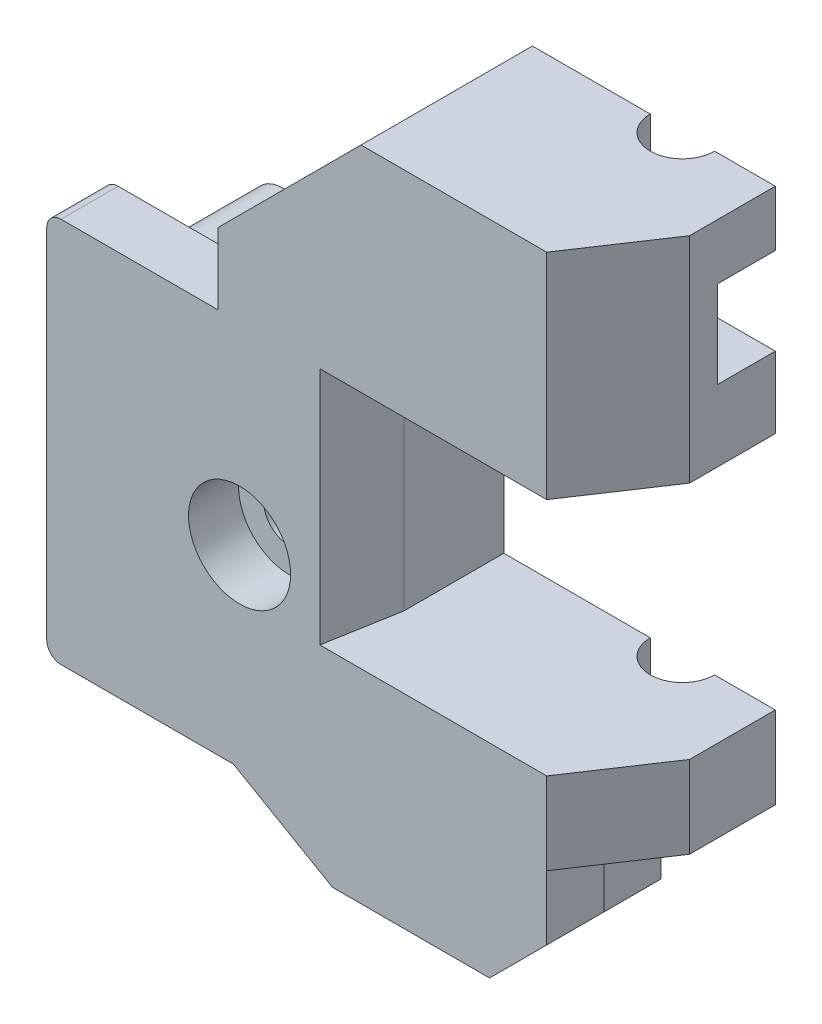
SolidWorks part; units mm, degrees
material "ABS"
ref_plane "Front Plane" through (0, 0, 0) normal (0, 0, 1) x (1, 0, 0)
ref_plane "Top Plane" through (0, 0, 0) normal (0, 1, 0) x (1, 0, 0)
ref_plane "Right Plane" through (0, 0, 0) normal (1, 0, 0) x (0, 0, -1)
sketch "Sketch2" plane through (0, 0, 0) normal (0, 0, 1) x (1, 0, 0)
  line L1 (1, 0) -> (20, 0)
  line L2 (0, 1) -> (0, 26)
  line L3 (1, 27) -> (20, 27)
  line L4 (20, 0) -> (20, 27)
  arc A0 (1, 0) -> (0, 1) centre (1, 1) cw
  arc A1 (1, 27) -> (0, 26) centre (1, 26) ccw
  point P3 (20, 0)
  point P6 (0, 0)
  point P10 (0, 27)
  dimension "D2" = 1
  dimension "D1" = 27
  dimension "D3" = 20
extrude "Boss-Extrude1" add sketch "Sketch2" along normal blind 4
sketch "Sketch3" plane through (0, 0, 0) normal (0, 0, 1) x (1, 0, 0)
  line L0 (4.5, 4.5) -> (4.5, 22.5) construction
  line L1 (1, 0) -> (20, 0) construction
  line L2 (0, 26) -> (0, 1) construction
  line L3 (3.5, 15.067) -> (3.5, 11.933)
  line L4 (0, 26) -> (0, 1) construction
  line L5 (12, 27) -> (12, 22.5)
  line L6 (20, 27) -> (1, 27) construction
  line L7 (20, 4.5) -> (15.2819, 4.5)
  line L8 (20, 0) -> (20, 27) construction
  line L9 (20, 0) -> (20, 27)
  line L10 (20, 0) -> (20, 27) construction
  circle A0 centre (4.5, 22.5) radius 2.15
  circle A1 centre (4.5, 4.5) radius 2.15
  circle A2 centre (4.5, 22.5) radius 7.5
  circle A3 centre (4.5, 4.5) radius 7.5
  arc A4 (11.5317, 7.1087) -> (3.5, 11.933) centre (4.5, 4.5) ccw
  arc A5 (11.5317, 7.1087) -> (15.2819, 4.5) centre (15.2819, 8.5) ccw
  point P28 (12, 4.5)
  line M13 (20, 27) -> (20, 0)
  line M14 (20, 0) -> (1, 0)
  line M18 (1, 27) -> (20, 27)
  dimension "D1" = 4.3
  dimension "D2" = 4.3
  dimension "D6" = 15
  dimension "D7" = 15
  dimension "D9" = 4
  dimension "D3" = 18
  dimension "D4" = 4.5
  dimension "D5" = 4.5
  dimension "D8" = 3.5
extrude "Boss-Extrude2" add sketch "Sketch3" against normal blind 8 contours A0 | A1
extrude "Boss-Extrude3" add sketch "Sketch3<3>" against normal up to surface (8 mm away) contours A3 L0 A2 M18 M13 M14 region at (14.6419, 15.3709, 0) up to face at (6.65, 22.5, -8)
sketch "Sketch3<3>" plane through (0, 0, 0) normal (0, 0, 1) x (1, 0, 0) same geometry as "Sketch3"
sketch "Sketch8" plane through (0, 0, 4) normal (0, 0, 1) x (1, 0, 0)
  line L0 (4.5, 13.5) -> (13.5, 13.5) construction
  line L6 (4.5, 15) -> (4.5, 12)
  line L7 (12, 27) -> (12, 22.5)
  line L8 (20, 27) -> (12, 27)
  line L9 (20, 4.5) -> (20, 27)
  line L12 (4.5, 15) -> (4.5, 12)
  line L13 (12, 27) -> (12, 22.5)
  line L14 (20, 27) -> (12, 27)
  line L15 (20, 4.5) -> (20, 27)
  line L17 (15.2819, 4.5) -> (20, 4.5)
  line L18 (15.2819, 4.5) -> (20, 4.5)
  arc A2 (4.5, 15) -> (12, 22.5) centre (4.5, 22.5) ccw
  arc A3 (11.5317, 7.1087) -> (4.5, 12) centre (4.5, 4.5) ccw
  arc A4 (4.5, 15) -> (12, 22.5) centre (4.5, 22.5) ccw
  arc A5 (11.5317, 7.1087) -> (4.5, 12) centre (4.5, 4.5) ccw
  arc A7 (11.5317, 7.1087) -> (15.2819, 4.5) centre (15.2819, 8.5) ccw
  arc A8 (11.5317, 7.1087) -> (15.2819, 4.5) centre (15.2819, 8.5) ccw
  point P2 (13.5, 13.5)
  dimension "D2" = 9
  dimension "D1" = 0
hole_wizard "CBORE for #6 Socket Head Cap Screw1" positions "Sketch10" profile "Sketch9" counterbore size "#6" standard "ANSI Inch" end condition through all
sketch "Sketch10" plane through (0, 0, 4) normal (0, 0, 1) x (1, 0, 0)
  point P0 (13.5, 13.5)
sketch "Sketch9" plane through (13.5, 13.5, 4) normal (1, 0, 0) x (0, -1, 0)
  line L0 (0, 0) -> (0, 12)
  line L1 (0, 12) -> (1.8288, 12)
  line L3 (1.8288, 12) -> (1.8288, 3.5052)
  line L4 (1.8288, 3.5052) -> (3.5725, 3.5052)
  line L5 (3.5725, 3.5052) -> (3.5725, 0)
  line L7 (3.5725, 0) -> (0, 0)
  line L11 (0, -6.35) -> (0, 107.95) construction
  dimension "Thru Hole Dia." = 3.6576
  dimension "Thru Hole Depth" = 12
  dimension "C'Bore Dia." = 7.145
  dimension "C'Bore Depth" = 3.5052
sketch "Sketch11" plane through (0, 27, 0) normal (0, 1, 0) x (1, 0, 0)
  line L0 (20, 8) -> (32.5, 8)
  line L1 (12, 0) -> (12, -4)
  line L2 (20, -4) -> (35, -4)
  line L3 (39, 2) -> (39, 8)
  line L4 (35, -4) -> (39, 2)
  line L5 (34.75, 8) -> (39, 8)
  line L6 (20, -4) -> (20, 8)
  line L7 (20, 8) -> (12, 8)
  line L8 (12, 8) -> (12, 0)
  line L9 (12, 0) -> (1, 0)
  line L10 (1, 0) -> (1, -4)
  line L11 (1, -4) -> (20, -4)
  line L12 (20, -4) -> (20, 8)
  line L13 (20, 8) -> (12, 8)
  line L14 (12, 8) -> (12, 0)
  line L15 (12, 0) -> (1, 0)
  line L16 (1, 0) -> (1, -4)
  line L17 (1, -4) -> (20, -4)
  line L18 (34.75, 8) -> (32.5, 8)
  circle A0 centre (32.5, 8) radius 7.5 construction
  circle A1 centre (32.5, 8) radius 2.25
  point P10 (39, -4)
  line M7 (20, -4) -> (20, 8)
  line M8 (20, 8) -> (12, 8)
  line M9 (12, 8) -> (12, 0)
  line M12 (1, -4) -> (20, -4)
  dimension "D3" = 15
  dimension "D4" = 4.5
  dimension "D2" = 12.5
  dimension "D5" = 6.5
  dimension "D7" = 6
  dimension "D6" = 4
  dimension "D1" = 0
extrude "Boss-Extrude5" add sketch "Sketch11" along normal blind 15 contours A1 L0 L2 L4 L3 L5 M7 | L1 M9 M12 M7 M8 | L0 A1 L18 region at (28.9143, 27, -2.0379) region at (16, 27, -2) region at (32.5, 27, -7.0451)
ref_plane "Plane1" through (0, 10.25, 0) normal (0, -1, 0) x (-1, 0, 0)
sketch "Sketch13" plane through (0, 10.25, 0) normal (0, -1, 0) x (-1, 0, 0)
  line L7 (-20, -4) -> (-20, 8)
  line L8 (-20, 8) -> (-39, 8)
  line L9 (-39, 8) -> (-39, 2)
  line L10 (-39, 2) -> (-35, -4)
  line L11 (-35, -4) -> (-20, -4)
  line L13 (-20, -4) -> (-20, 8)
  line L14 (-20, 8) -> (-39, 8)
  line L15 (-39, 8) -> (-39, 2)
  line L16 (-39, 2) -> (-35, -4)
  line L17 (-35, -4) -> (-20, -4)
  dimension "D1" = 0
extrude "Boss-Extrude6" add sketch "Sketch13" along normal up to surface (5.75 mm away) up to face at (17.641, 4.5, -4)
extrude "Cut-Extrude1" cut sketch "Sketch11<5>" against normal offset from surface 2.5 and the other way through all contours A1 up to face at (26.2234, 4.5, -1.4286)
sketch "Sketch11<5>" plane through (0, 27, 0) normal (0, 1, 0) x (1, 0, 0) same geometry as "Sketch11"
ref_plane "Plane2" through (0, 32, 0) normal (0, -1, 0) x (-1, 0, 0)
sketch "Sketch14" plane through (0, 32, 0) normal (0, -1, 0) x (-1, 0, 0)
  line L1 (-29.85, 1.45) -> (-24.85, 1.45)
  line L2 (-29.85, 1.45) -> (-29.85, 14.55)
  line L3 (-29.85, 14.55) -> (-24.85, 14.55)
  line L4 (-24.85, 1.45) -> (-24.85, 14.55)
  line L5 (-24.85, 14.55) -> (-9.85, 14.55)
  line L6 (-24.85, 14.55) -> (-24.85, 1.45)
  line L7 (-24.85, 1.45) -> (-9.85, 1.45)
  line L8 (-9.85, 14.55) -> (-9.85, 1.45)
  arc A0 (-34.75, 8) -> (-30.25, 8) centre (-32.5, 8) ccw construction
  arc A1 (-34.75, 8) -> (-30.25, 8) centre (-32.5, 8) ccw construction
  circle A2 centre (-32.5, 8) radius 7.6 construction
  circle A3 centre (-32.5, 8) radius 7.65
  point P10 (-24.85, 8)
  dimension "D1" = 15.2
  dimension "D3" = 13.1
  dimension "D4" = 5
  dimension "D5" = 15
  dimension "D2" = 0.05
extrude "Cut-Extrude2" cut sketch "Sketch14" against normal blind 6.1 contours A3 L6 L3 | A3 L1 L4 | L8 L5 L6 L4 L7 | A3 region at (25.8912, 32, -2.998) region at (17.35, 32, -8) region at (25.8912, 32, -13.002)
chamfer "Chamfer2" distance 10 angle 45 1 edges at (12, 42, -2)
sketch "Sketch18" plane through (0, 0, -8) normal (0, 0, -1) x (-1, 0, 0)
  line L0 (-20, 26.1163) -> (-12, 26.1163) construction
  line L1 (-20, 10.25) -> (-20, 27) construction
  line L2 (-12, 27) -> (-12, 22.5) construction
  line L3 (-16, 26.1163) -> (-16, 16.205) construction
  line L4 (-12, 32) -> (-30.25, 32) construction
  circle A0 centre (-16, 26) radius 2
  dimension "D1" = 4
  dimension "D2" = 6
extrude "Boss-Extrude10" add sketch "Sketch18" along normal blind 2
chamfer "Chamfer3" distance 5 angle 10 1 edges at (20, 18.625, 4) first distance on face at (20, 18.625, -2)
sketch "Sketch15" plane through (0, 0, 4) normal (0, 0, 1) x (1, 0, 0)
  line L0 (20, 0) -> (20, -4)
  line L1 (20, -4) -> (13.0718, 0)
  line L2 (1, 0) -> (20, 0) construction
  line L3 (20, -4) -> (31, -4)
  line L4 (35, 0) -> (35, 4.5)
  line L5 (31, -4) -> (35, 0)
  point P6 (35, -4)
  line M12 (1, 0) -> (20, 0)
  line M13 (20, 0) -> (20, 4.5)
  line M14 (20, 4.5) -> (35, 4.5)
  dimension "D1" = 4
  dimension "D2" = 60
extrude "Boss-Extrude7" add sketch "Sketch15" against normal up to surface (4 mm away) contours L3 L4 L0 M14 M13 | L1 L0 M12 region at (27.0872, 0.4453, 4) region at (17.6906, -1.3333, 4) up to face at (6.65, 4.5, 0)
sketch "Sketch17" plane through (0, 0, 0) normal (0, 0, -1) x (-1, 0, 0)
  line L0 (-30.25, 0) -> (-15.8708, 0)
  line L8 (-35, 4.5) -> (-35, 0)
  line L9 (-35, 0) -> (-31, -4)
  line L11 (-15.2819, 4.5) -> (-35, 4.5)
  line L14 (-31, -0.75) -> (-31, -4)
  line L15 (-31, -4) -> (-20, -4)
  line L16 (-13.0718, 0) -> (-1, 0)
  line L17 (0, 1) -> (0, 26)
  line L18 (-1, 27) -> (-12, 27)
  line L19 (-12, 27) -> (-12, 22.5)
  line L20 (-4.5, 15) -> (-4.5, 12)
  line L21 (-31, -4) -> (-20, -4)
  line L22 (-20, -4) -> (-13.0718, 0)
  line L23 (-20, -4) -> (-15.4958, -1.3995)
  arc A0 (-15.4958, -1.3995) -> (-15.8708, 0) centre (-15.8708, -0.75) ccw
  arc A1 (-30.25, 0) -> (-31, -0.75) centre (-30.25, -0.75) ccw
  arc A4 (-1, 0) -> (0, 1) centre (-1, 1) ccw
  arc A5 (0, 26) -> (-1, 27) centre (-1, 26) ccw
  arc A6 (-12, 22.5) -> (-4.5, 15) centre (-4.5, 22.5) ccw
  arc A7 (-4.5, 12) -> (-11.5317, 7.1087) centre (-4.5, 4.5) ccw
  arc A11 (-15.2819, 4.5) -> (-11.5317, 7.1087) centre (-15.2819, 8.5) ccw
  arc A12 (-15.2819, 4.5) -> (-11.5317, 7.1087) centre (-15.2819, 8.5) ccw
  dimension "D2" = 0.75
  dimension "D1" = 0
extrude "Boss-Extrude9" add sketch "Sketch17" along normal up to surface (8 mm away) contours L0 A0 L23 L21 L14 A1 up to face at (23.1391, 14.8481, -8)
